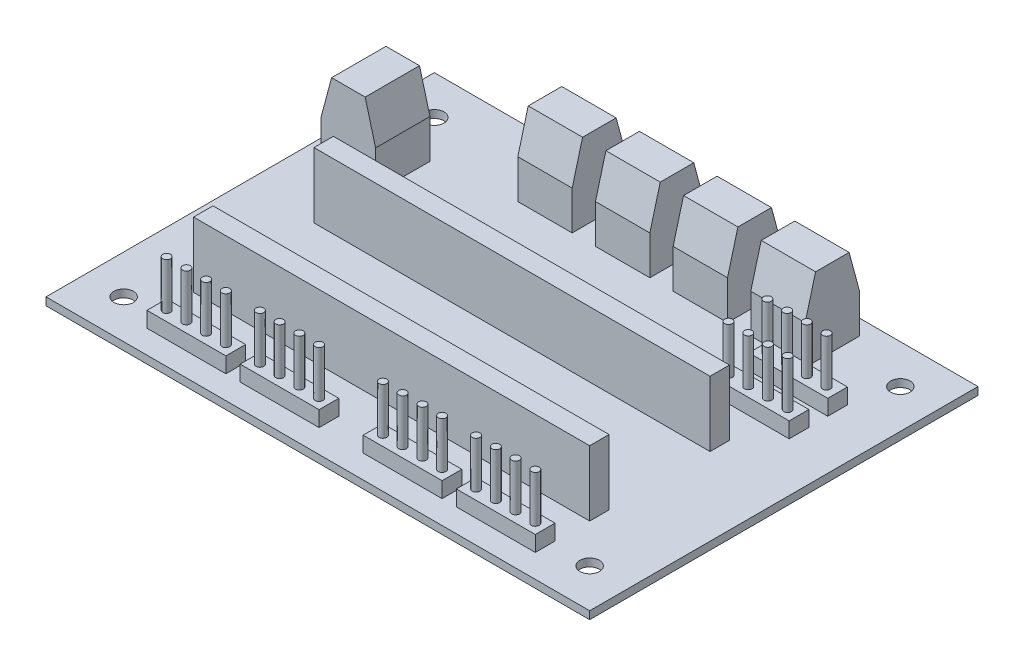
SolidWorks part; units mm, degrees
material "ABS"
ref_plane "Спереди" through (0, 0, 0) normal (0, 0, 1) x (1, 0, 0)
ref_plane "Сверху" through (0, 0, 0) normal (0, 1, 0) x (1, 0, 0)
ref_plane "Справа" through (0, 0, 0) normal (1, 0, 0) x (0, 0, -1)
sketch "Эскиз2" plane through (0, 0, 0) normal (0, 1, 0) x (1, 0, 0)
  line L0 (0, 25) -> (113.3637, 25) construction
  line L1 (0, 0) -> (70, 0)
  line L2 (0, 0) -> (0, 50)
  line L3 (0, 50) -> (70, 50)
  line L4 (70, 0) -> (70, 50)
  line L5 (35, 50) -> (35, -7.1391) construction
  circle A0 centre (5, 45) radius 1.25
  circle A1 centre (65, 45) radius 1.25
  circle A2 centre (65, 5) radius 1.25
  circle A3 centre (5, 5) radius 1.25
  dimension "D3" = 2.5
  dimension "D1" = 70
  dimension "D2" = 50
  dimension "D4" = 5
  dimension "D5" = 5
extrude "Бобышка-Вытянуть1" add sketch "Эскиз2" along normal blind 1
sketch "Эскиз3" plane through (0, 1, 0) normal (0, 1, 0) x (1, 0, 0)
  line L0 (0, 0) -> (70, 0) construction
  line L1 (9, 12.5) -> (60, 12.5)
  line L2 (9, 12.5) -> (9, 10)
  line L3 (9, 10) -> (60, 10)
  line L4 (60, 12.5) -> (60, 10)
  line L9 (70, 0) -> (70, 50) construction
  line L10 (60, 12.5) -> (60, 19) construction
  line L11 (60, 19) -> (7.0253, 19) construction
  line L12 (9, 28) -> (60, 28)
  line L13 (60, 25.5) -> (60, 28)
  line L14 (9, 25.5) -> (60, 25.5)
  line L15 (9, 25.5) -> (9, 28)
  dimension "D1" = 2.5
  dimension "D2" = 51
  dimension "D6" = 10
  dimension "D7" = 10
extrude "Бобышка-Вытянуть2" add sketch "Эскиз3" along normal blind 8.4
sketch "Эскиз4" plane through (0, 1, 0) normal (0, 1, 0) x (1, 0, 0)
  line L0 (70, 0) -> (70, 50) construction
  line L1 (60, 5.54) -> (49.84, 5.54)
  line L2 (60, 5.54) -> (60, 3)
  line L3 (60, 3) -> (49.84, 3)
  line L4 (49.84, 5.54) -> (49.84, 3)
  line L5 (0, 0) -> (70, 0) construction
  line L6 (48, 5.54) -> (48, 3)
  line L7 (35, 0) -> (35, 38.4524) construction
  line L8 (48, 5.54) -> (37.84, 5.54)
  line L9 (37.84, 5.54) -> (37.84, 3)
  line L10 (48, 3) -> (37.84, 3)
  line L11 (10, 3) -> (20.16, 3)
  line L12 (20.16, 5.54) -> (20.16, 3)
  line L13 (10, 5.54) -> (20.16, 5.54)
  line L14 (10, 5.54) -> (10, 3)
  line L15 (22, 5.54) -> (32.16, 5.54)
  line L16 (32.16, 5.54) -> (32.16, 3)
  line L17 (22, 3) -> (32.16, 3)
  line L18 (22, 5.54) -> (22, 3)
  line L19 (53.4823, 37.0132) -> (63.6423, 37.0132)
  line L20 (53.4823, 37.0132) -> (53.4823, 39.5532)
  line L21 (53.4823, 39.5532) -> (63.6423, 39.5532)
  line L22 (63.6423, 37.0132) -> (63.6423, 39.5532)
  line L23 (53.5146, 32.0132) -> (63.6746, 32.0132)
  line L24 (53.5146, 32.0132) -> (53.5146, 34.5532)
  line L25 (53.5146, 34.5532) -> (63.6746, 34.5532)
  line L26 (63.6746, 32.0132) -> (63.6746, 34.5532)
  point P30 (0, 0)
  dimension "D1" = 2.54
  dimension "D2" = 10.16
  dimension "D3" = 10
  dimension "D4" = 3
  dimension "D6" = 5
  dimension "D5" = 2
extrude "Бобышка-Вытянуть3" add sketch "Эскиз4" along normal blind 2
sketch "Эскиз5" plane through (0, 3, 0) normal (0, 1, 0) x (1, 0, 0)
  line L0 (60, 3) -> (60, 5.54) construction
  line L1 (49.84, 3) -> (60, 3) construction
  line L2 (35, 0) -> (35, 20.127) construction
  line L3 (0, 0) -> (70, 0) construction
  circle A0 centre (58.73, 4.27) radius 0.5
  circle A1 centre (56.19, 4.27) radius 0.5
  circle A2 centre (53.65, 4.27) radius 0.5
  circle A3 centre (51.11, 4.27) radius 0.5
  circle A4 centre (46.73, 4.27) radius 0.5
  circle A5 centre (44.19, 4.27) radius 0.5
  circle A6 centre (41.65, 4.27) radius 0.5
  circle A7 centre (39.11, 4.27) radius 0.5
  circle A8 centre (25.81, 4.27) radius 0.5
  circle A9 centre (11.27, 4.27) radius 0.5
  circle A10 centre (13.81, 4.27) radius 0.5
  circle A11 centre (16.35, 4.27) radius 0.5
  circle A12 centre (18.89, 4.27) radius 0.5
  circle A13 centre (23.27, 4.27) radius 0.5
  circle A14 centre (28.35, 4.27) radius 0.5
  circle A15 centre (30.89, 4.27) radius 0.5
  circle A16 centre (54.671, 33.2084) radius 0.5
  circle A17 centre (54.671, 38.2084) radius 0.5
  circle A20 centre (57.211, 33.2084) radius 0.5
  circle A21 centre (59.751, 33.2084) radius 0.5
  circle A22 centre (62.291, 33.2084) radius 0.5
  circle A23 centre (57.211, 38.2084) radius 0.5
  circle A24 centre (59.751, 38.2084) radius 0.5
  circle A25 centre (62.291, 38.2084) radius 0.5
  dimension "D1" = 1
  dimension "D2" = 1.27
  dimension "D3" = 1.27
  dimension "D4" = 4
  dimension "D5" = 2
  dimension "D6" = 4
  dimension "D7" = 2
extrude "Бобышка-Вытянуть4" add sketch "Эскиз5" along normal blind 6
sketch "Эскиз6" plane through (0, 1, 0) normal (0, 1, 0) x (1, 0, 0)
  line L0 (19.7472, 48.0002) -> (26.7472, 48.0002)
  line L5 (2.608, 39.8256) -> (9.608, 39.8256)
  line L6 (2.608, 39.8256) -> (2.608, 32.8256)
  line L7 (2.608, 32.8256) -> (9.608, 32.8256)
  line L8 (9.608, 39.8256) -> (9.608, 32.8256)
  line L9 (19.7472, 48.0002) -> (19.7472, 41.0002)
  line L10 (19.7472, 41.0002) -> (26.7472, 41.0002)
  line L11 (26.7472, 48.0002) -> (26.7472, 41.0002)
  line L12 (29.7472, 48.0002) -> (36.7472, 48.0002)
  line L13 (36.7472, 48.0002) -> (36.7472, 41.0002)
  line L14 (29.7472, 41.0002) -> (36.7472, 41.0002)
  line L15 (29.7472, 48.0002) -> (29.7472, 41.0002)
  line L16 (39.7472, 48.0002) -> (46.7472, 48.0002)
  line L17 (46.7472, 48.0002) -> (46.7472, 41.0002)
  line L18 (39.7472, 41.0002) -> (46.7472, 41.0002)
  line L19 (39.7472, 48.0002) -> (39.7472, 41.0002)
  line L20 (49.7472, 48.0002) -> (56.7472, 48.0002)
  line L21 (56.7472, 48.0002) -> (56.7472, 41.0002)
  line L22 (49.7472, 41.0002) -> (56.7472, 41.0002)
  line L23 (49.7472, 48.0002) -> (49.7472, 41.0002)
  dimension "D1" = 7
  dimension "D2" = 7
  dimension "D3" = 4
extrude "Бобышка-Вытянуть5" add sketch "Эскиз6" along normal blind 10
chamfer "Фаска1" distance 5 angle 15 10 edges at (53.2472, 11, -48.0002) (53.2472, 11, -41.0002) (43.2472, 11, -48.0002) (43.2472, 11, -41.0002) (33.2472, 11, -41.0002) (33.2472, 11, -48.0002) (23.2472, 11, -48.0002) (23.2472, 11, -41.0002) (9.608, 11, -36.3256) (2.608, 11, -36.3256) first distance on face at (53.2472, 6, -48.0002) first distance on face at (53.2472, 6, -41.0002) first distance on face at (43.2472, 6, -48.0002) first distance on face at (43.2472, 6, -41.0002) first distance on face at (33.2472, 6, -41.0002) first distance on face at (33.2472, 6, -48.0002) first distance on face at (23.2472, 6, -48.0002) first distance on face at (23.2472, 6, -41.0002) first distance on face at (9.608, 6, -36.3256) first distance on face at (2.608, 6, -36.3256)
